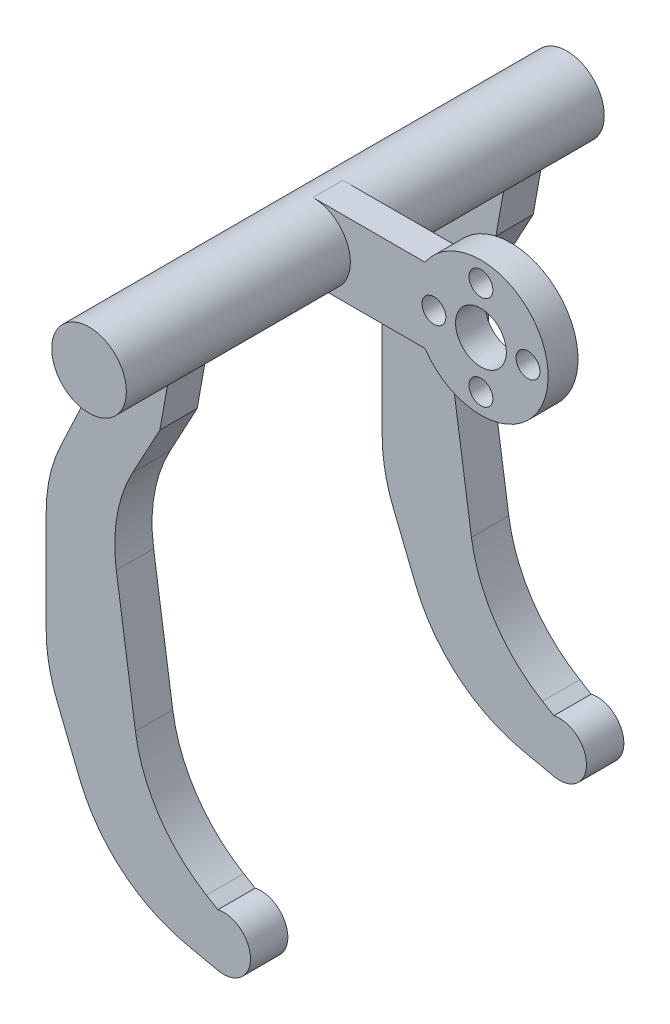
SolidWorks part; units mm, degrees
ref_plane "Front Plane" through (0, 0, 0) normal (0, 0, 1) x (1, 0, 0)
ref_plane "Top Plane" through (0, 0, 0) normal (0, 1, 0) x (1, 0, 0)
ref_plane "Right Plane" through (0, 0, 0) normal (1, 0, 0) x (0, 0, -1)
sketch "Sketch2" plane through (0, 0, 0) normal (0, 0, 1) x (1, 0, 0)
  circle A0 centre (0, 0) radius 11.43
  dimension "D1" = 22.86
extrude "Boss-Extrude1" add sketch "Sketch2" along normal blind 5.08
sketch "Sketch4" plane through (0, 0, 0) normal (0, 0, -1) x (-1, 0, 0)
  circle A0 centre (0, 0) radius 4.318
  circle A1 centre (0, -8.001) radius 2.032
  dimension "D1" = 8.001
extrude "Cut-Extrude1" cut sketch "Sketch4" against normal blind 5.08
sketch "Sketch7" plane through (0, 0, 0) normal (0, 0, -1) x (-1, 0, 0)
  line L1 (9.5038, 6.35) -> (28.5538, 6.35)
  line L2 (9.5038, 6.35) -> (9.5038, -6.35)
  line L3 (9.5038, -6.35) -> (28.5538, -6.35)
  circle A0 centre (0, 0) radius 11.43 construction
  arc A1 (28.5538, 6.35) -> (28.5538, -6.35) centre (28.5538, 0) cw
  dimension "D1" = 12.7
  dimension "D2" = 19.05
  dimension "D3" = 6.35
extrude "Boss-Extrude2" add sketch "Sketch7" against normal blind 5.08
pattern_circular "CirPattern1" count 4 over 360 about axis through (0, 0, 5.08) along (0, 0, -1) of "Cut-Extrude1"
sketch "Sketch9" plane through (0, 0, 5.08) normal (0, 0, 1) x (1, 0, 0)
  circle A0 centre (-28.5538, 0) radius 6.35
extrude "Boss-Extrude3" add sketch "Sketch9" along normal blind 38.1 and the other way blind 43.18
ref_plane "Plane1" through (0, 0, -31.75) normal (0, 0, 1) x (1, 0, 0)
ref_plane "Plane2" through (-27.94, 0, 0) normal (1, 0, 0) x (0, 0, -1)
sketch "Sketch12" plane through (0, 0, -31.75) normal (0, 0, 1) x (1, 0, 0)
  line L0 (-33.0479, 0) -> (-25.3788, 0)
  line L1 (-33.0479, 0) -> (-47.2674, -30.2454)
  line L2 (-47.2674, -58.3342) -> (-36.5753, -84.8679)
  line L3 (-36.5753, -84.8679) -> (-18.0737, -88.9)
  line L4 (-18.0737, -79.96) -> (-30.3458, -72.6081)
  line L5 (-30.3458, -72.6081) -> (-36.5753, -30.2454)
  line L6 (-47.2674, -30.2454) -> (-47.2674, -58.3342)
  line L7 (-27.94, -12.573) -> (-27.94, 12.573) construction
  line L8 (-27.94, -14.2497) -> (-25.3788, 0)
  line L10 (-36.5753, -30.2454) -> (-27.94, -14.2497)
  line L11 (-25.3788, 0) -> (-25.652, -0.0259)
  arc A0 (-18.0737, -88.9) -> (-18.0737, -79.96) centre (-17.0995, -84.43) ccw
extrude "Boss-Extrude4" add sketch "Sketch12" along normal blind 6.35 contours L3 A0 L4 L5 L10 L8 L0 L1 L6 L2 region at (-35.3637, -49.237, -31.75)
fillet "Fillet1" radius 25.4 5 edges at (-36.5753, -30.2454, -28.575) (-30.3458, -72.6081, -28.575) (-36.5753, -84.8679, -28.575) (-47.2674, -58.3342, -28.575) (-47.2674, -30.2454, -28.575)
mirror "Mirror1" about plane through (0, 0, 0) normal (0, 0, 1) of "Fillet1", "Boss-Extrude4"
